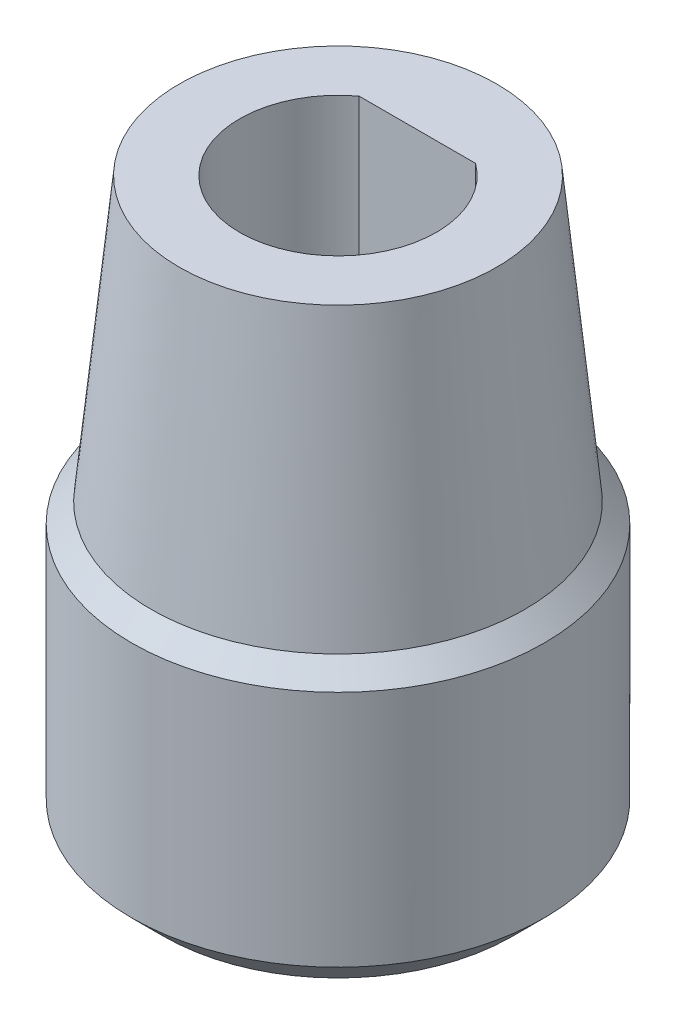
SolidWorks part; units mm, degrees
ref_plane "Front Plane" through (0, 0, 0) normal (0, 0, 1) x (1, 0, 0)
ref_plane "Top Plane" through (0, 0, 0) normal (0, 1, 0) x (1, 0, 0)
ref_plane "Right Plane" through (0, 0, 0) normal (1, 0, 0) x (0, 0, -1)
sketch "Sketch1" plane through (0, 0, 0) normal (0, 1, 0) x (1, 0, 0)
  line L0 (-1.833, 2.5) -> (1.833, 2.5)
  circle A0 centre (0, 0) radius 4.5
  circle A1 centre (0, 0) radius 3.1
  circle A2 centre (0, 0) radius 6
  circle A3 centre (0, 0) radius 6.5
  dimension "D1" = 9
  dimension "D2" = 6.2
  dimension "D4" = 12
  dimension "D5" = 13
  dimension "D3" = 2.5
extrude "Boss-Extrude1" add sketch "Sketch1" along normal blind 10 contours A2 A1 | L0 A1 | A2 A0 region at (0, 0, -2.7421) region at (-4.3727, 0, 0) region at (-5.8303, 0, 0)
extrude "Boss-Extrude2" add sketch "Sketch1<3>" along normal blind 3 contours A2 A1 | A1 region at (-4.3727, 0, 0)
sketch "Sketch1<3>" plane through (0, 0, 0) normal (0, 1, 0) x (1, 0, 0) same geometry as "Sketch1"
extrude "Boss-Extrude3" add sketch "Sketch1<6>" against normal blind 8 contours A3 A0 | A2 A0 region at (-5.8303, 0, 0) region at (-6.3162, 0, 0)
sketch "Sketch1<6>" plane through (0, 0, 0) normal (0, 1, 0) x (1, 0, 0) same geometry as "Sketch1"
chamfer "Chamfer1" distance 1 distance2 1 1 edges at (0, 0, 6)
chamfer "Chamfer2" distance 10 distance2 1 1 edges at (0, 10, 6) first distance on face at (0, 1, 6)
chamfer "Chamfer3" distance 1 angle 45 1 edges at (0, -8, 6.5)
thread "Thread1" pitch 1.5 method cut profile "Thread Profile1" start angle 0, offset 1, length 0, pitch 1.5, diameter 9
ref_plane "Plane1" through (4.5, -9, 0) normal (0, 0, 1) x (1, 0, 0)
sketch "Thread Profile1" plane through (4.5, -9, 0) normal (0, 0, 1) x (1, 0, 0)
  line L0 (0, 0) -> (0, 1.5) construction
  line L1 (0, 0) -> (0.8119, 0.4687)
  line L2 (0.8119, 0.4687) -> (0.8119, 0.6562)
  line L3 (0.8119, 0.6562) -> (0, 1.125)
  line L4 (0.8119, 0.5625) -> (0, 0.5625) construction
  line L11 (0, 0) -> (0, 1.125)
  point P2 (0, 0)
  dimension "Pitch" = 1.5
  dimension "Profile_Angle" = 60
  dimension "Profile_Land" = 0.1875
  dimension "Profile_Height" = 0.8119
